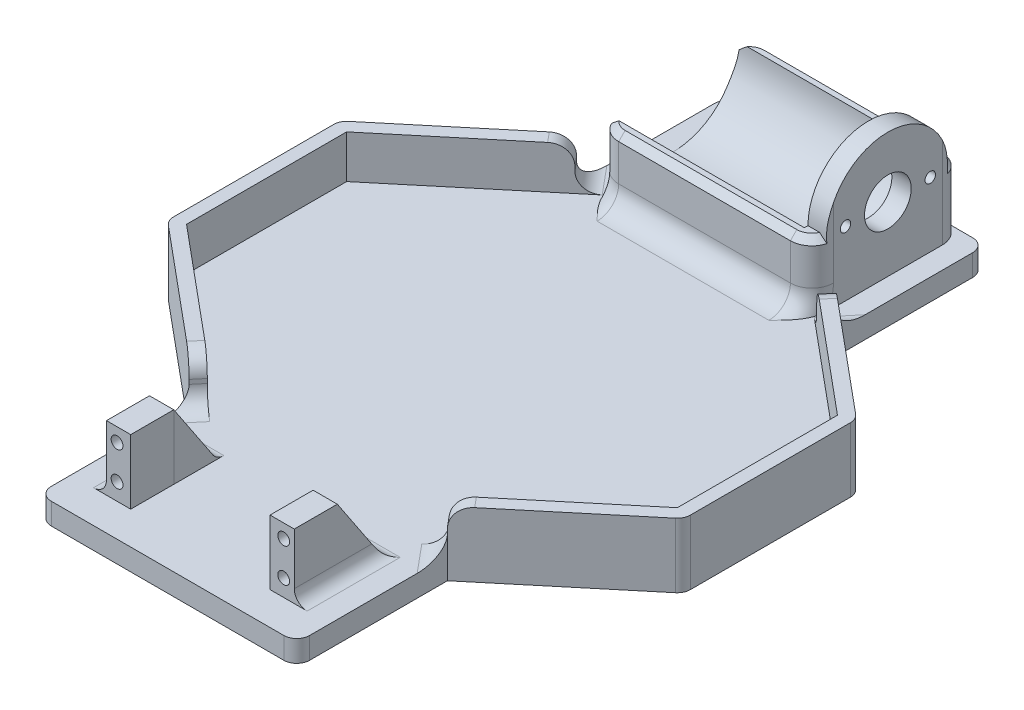
SolidWorks part; units mm, degrees
ref_plane "Front Plane" through (0, 0, 0) normal (0, 0, 1) x (1, 0, 0)
ref_plane "Top Plane" through (0, 0, 0) normal (0, 1, 0) x (1, 0, 0)
ref_plane "Right Plane" through (0, 0, 0) normal (1, 0, 0) x (0, 0, -1)
sketch "Sketch1" plane through (0, 0, 0) normal (0, 1, 0) x (1, 0, 0)
  line L0 (-34.29, 0) -> (34.29, 0)
  line L1 (0, 0) -> (0, 203.2) construction
  line L2 (-34.29, 203.2) -> (34.29, 203.2)
  line L3 (0, 101.6) -> (76.2, 101.6) construction
  line L4 (38.1, 199.39) -> (38.1, 158.75)
  line L5 (38.1, 158.75) -> (74.8291, 128.1424)
  line L6 (76.2, 125.2155) -> (76.2, 77.9845)
  line L7 (38.1, 44.45) -> (74.8291, 75.0576)
  line L8 (38.1, 3.81) -> (38.1, 44.45)
  line L9 (0, 0) -> (34.29, 0)
  line L10 (-38.1, 3.81) -> (-38.1, 44.45)
  line L11 (-38.1, 44.45) -> (-74.8291, 75.0576)
  line L12 (-76.2, 125.2155) -> (-76.2, 77.9845)
  line L13 (-38.1, 158.75) -> (-74.8291, 128.1424)
  line L14 (-38.1, 199.39) -> (-38.1, 158.75)
  arc A0 (38.1, 199.39) -> (34.29, 203.2) centre (34.29, 199.39) ccw
  arc A1 (76.2, 125.2155) -> (74.8291, 128.1424) centre (72.39, 125.2155) ccw
  arc A2 (76.2, 77.9845) -> (74.8291, 75.0576) centre (72.39, 77.9845) cw
  arc A3 (38.1, 3.81) -> (34.29, 0) centre (34.29, 3.81) cw
  arc A4 (-38.1, 3.81) -> (-34.29, 0) centre (-34.29, 3.81) ccw
  arc A5 (-76.2, 77.9845) -> (-74.8291, 75.0576) centre (-72.39, 77.9845) ccw
  arc A6 (-76.2, 125.2155) -> (-74.8291, 128.1424) centre (-72.39, 125.2155) cw
  arc A7 (-38.1, 199.39) -> (-34.29, 203.2) centre (-34.29, 199.39) cw
  point P11 (-93.4544, 210.6955)
  point P14 (38.1, 203.2)
  point P17 (76.2, 127)
  point P20 (76.2, 76.2)
  dimension "D1" = 3.81
  dimension "D2" = 203.2
  dimension "D3" = 76.2
  dimension "D4" = 38.1
  dimension "D5" = 25.4
  dimension "D6" = 44.45
extrude "Boss-Extrude1" add sketch "Sketch1" along normal blind 6.35 contours A7 L14 L13 A6 L12 A5 L11 L10 A4 L0 A3 L8 L7 A2 L6 A1 L5 L4 A0 L2 region at (0, 0, -101.6)
sketch "Sketch2" plane through (0, 6.35, 0) normal (0, 1, 0) x (1, 0, 0)
  line L0 (0, 0) -> (0, 9.6774) construction
  line L1 (-27.6987, 9.6774) -> (-27.6987, 22.3774)
  line L2 (-20.5486, 9.6774) -> (-27.6987, 9.6774)
  line L3 (20.5486, 9.6774) -> (27.6987, 9.6774)
  line L4 (-27.6987, 22.3774) -> (-20.5486, 22.3774)
  line L5 (-20.5486, 22.3774) -> (-20.5486, 9.6774)
  line L6 (27.6987, 22.3774) -> (20.5486, 22.3774)
  line L7 (27.6987, 9.6774) -> (27.6987, 22.3774)
  line L8 (20.5486, 22.3774) -> (20.5486, 9.6774)
  point P6 (0, 9.6774)
  point P12 (0, 0)
  point P14 (-29.2604, 13.1532)
  dimension "D1" = 9.6774
  dimension "D2" = 41.0972
  dimension "D4" = 12.7
extrude "Boss-Extrude2" add sketch "Sketch2" along normal blind 19.05 contours L6 L8 L3 L7 | L5 L2 L1 L4 region at (24.1236, 6.35, -16.0274)
sketch "Sketch3" plane through (-27.6987, 0, 0) normal (-1, 0, 0) x (0, 0, 1)
  line L0 (-22.3774, 25.4) -> (-35.0774, 6.35)
  line L1 (-3.81, 6.35) -> (-44.45, 6.35) construction
  line L2 (-35.0774, 6.35) -> (-22.3774, 6.35)
  line L3 (-22.3774, 6.35) -> (-22.3774, 25.4)
  dimension "D1" = 12.7
extrude "Boss-Extrude3" add sketch "Sketch3" against normal blind 7.1628
ref_plane "Plane1" through (0, 0, 0) normal (-1, 0, 0) x (0, 0, 1)
mirror "Mirror1" about plane through (0, 0, 0) normal (-1, 0, 0) of "Boss-Extrude3"
fillet "Fillet1" radius 3.81 4 edges at (27.6987, 6.35, -22.3774) (24.1173, 6.35, -35.0774) (-24.1173, 6.35, -35.0774) (-27.6987, 6.35, -22.3774)
sketch "Sketch4" plane through (0, 6.35, 0) normal (0, 1, 0) x (1, 0, 0)
  line L0 (-38.1, 158.75) -> (-74.8291, 128.1424)
  line L1 (-76.2, 125.2155) -> (-76.2, 77.9845) construction
  line L2 (-76.2, 125.2155) -> (-76.2, 77.9845)
  line L3 (-74.8291, 75.0576) -> (-38.1, 44.45)
  line L4 (-35.6609, 155.8231) -> (-72.39, 125.2155)
  line L5 (-72.39, 125.2155) -> (-72.39, 77.9845)
  line L6 (-72.39, 77.9845) -> (-35.6609, 47.3769)
  line L7 (-38.1, 44.45) -> (-35.6609, 47.3769)
  line L8 (-38.1, 158.75) -> (-35.6609, 155.8231)
  line L9 (0, 8.382) -> (0, -8.382) construction
  line L10 (35.6609, 155.8231) -> (72.39, 125.2155)
  line L11 (38.1, 158.75) -> (74.8291, 128.1424)
  line L12 (72.39, 125.2155) -> (72.39, 77.9845)
  line L13 (76.2, 125.2155) -> (76.2, 77.9845)
  line L14 (38.1, 44.45) -> (35.6609, 47.3769)
  line L15 (74.8291, 75.0576) -> (38.1, 44.45)
  line L16 (72.39, 77.9845) -> (35.6609, 47.3769)
  line L17 (38.1, 158.75) -> (35.6609, 155.8231)
  arc A0 (-74.8291, 128.1424) -> (-76.2, 125.2155) centre (-72.39, 125.2155) ccw
  arc A1 (-76.2, 77.9845) -> (-74.8291, 75.0576) centre (-72.39, 77.9845) ccw
  arc A2 (-72.39, 125.2155) -> (-72.39, 125.2155) centre (-72.39, 125.2155) ccw
  arc A3 (-72.39, 77.9845) -> (-72.39, 77.9845) centre (-72.39, 77.9845) ccw
  arc A4 (74.8291, 128.1424) -> (76.2, 125.2155) centre (72.39, 125.2155) cw
  arc A5 (76.2, 77.9845) -> (74.8291, 75.0576) centre (72.39, 77.9845) cw
  dimension "D1" = 3.81
extrude "Boss-Extrude4" add sketch "Sketch4" along normal blind 12.7
fillet "Fillet3" radius 5.715 8 edges at (36.8804, 6.35, -45.9135) (-36.8804, 6.35, -45.9135) (36.8804, 6.35, -157.2865) (-36.8804, 6.35, -157.2865) (36.8804, 19.05, -157.2865) (-36.8804, 19.05, -157.2865) (36.8804, 19.05, -45.9135) (-36.8804, 19.05, -45.9135)
sketch "Sketch6" plane through (0, 0, -9.6774) normal (0, 0, 1) x (1, 0, 0)
  line L0 (-34.29, 6.35) -> (34.29, 6.35) construction
  line L1 (-20.5359, 6.35) -> (-20.5359, 25.4) construction
  circle A0 centre (-24.5745, 11.3538) radius 1.7399
  circle A1 centre (-24.5745, 21.3614) radius 1.7399
  dimension "D4" = 3.4798
  dimension "D5" = 3.4798
  dimension "D1" = 5.0038
  dimension "D2" = 4.0386
  dimension "D3" = 15.0114
extrude "Cut-Extrude1" cut sketch "Sketch6" against normal blind 7.62
mirror "Mirror2" about plane through (0, 0, 0) normal (-1, 0, 0) of "Cut-Extrude1"
sketch "Sketch7" plane through (0, 6.35, 0) normal (0, 1, 0) x (1, 0, 0)
  line L0 (0, 203.2) -> (0, 158.3944) construction
  line L1 (-34.29, 203.2) -> (34.29, 203.2) construction
  line L3 (-31.6738, 158.3944) -> (31.6738, 158.3944)
  line L4 (-31.6738, 158.3944) -> (-31.6738, 203.2)
  line L5 (-31.6738, 203.2) -> (31.6738, 203.2)
  line L6 (31.6738, 158.3944) -> (31.6738, 203.2)
  line L7 (-31.6738, 158.3944) -> (31.6738, 203.2) construction
  line L8 (-31.6738, 203.2) -> (31.6738, 158.3944) construction
  point P5 (0, 180.7972)
  dimension "D1" = 44.8056
  dimension "D2" = 63.3476
extrude "Boss-Extrude5" add sketch "Sketch7" along normal blind 38.1
sketch "Sketch8" plane through (-31.6738, 0, 0) normal (-1, 0, 0) x (0, 0, 1)
  line L0 (-180.7972, 6.35) -> (-180.7972, 6.4897) construction
  line L1 (-161.8869, 25.4) -> (-158.3944, 25.4)
  line L2 (-203.2, 44.45) -> (-158.3944, 44.45) construction
  line L3 (-158.3944, 44.45) -> (-158.3944, 6.35) construction
  line L4 (-203.2, 44.45) -> (-158.3944, 44.45)
  line L5 (-203.2, 44.45) -> (-203.2, 25.4)
  line L6 (-203.2, 25.4) -> (-199.7075, 25.4)
  line L7 (-158.3944, 44.45) -> (-158.3944, 25.4)
  line L8 (-180.7972, 44.3103) -> (-180.7972, 44.45) construction
  arc A0 (-199.7075, 25.4) -> (-161.8869, 25.4) centre (-180.7972, 25.4) ccw
  dimension "D1" = 37.8206
extrude "Cut-Extrude2" cut sketch "Sketch8" against normal blind 57.6326
sketch "Sketch10" plane through (31.6738, 0, 0) normal (1, 0, 0) x (0, 0, -1)
  line L0 (180.7972, 6.35) -> (180.7972, 7.5184) construction
  line L4 (158.3944, 6.35) -> (203.2, 6.35) construction
  line L5 (203.2, 44.45) -> (203.2, 6.35) construction
  line L7 (158.3944, 44.45) -> (203.2, 44.45)
  line L8 (158.3944, 44.45) -> (158.3944, 25.4)
  line L9 (158.3944, 25.4) -> (162.941, 25.4)
  line L10 (203.2, 44.45) -> (203.2, 25.4)
  line L11 (198.6534, 25.4) -> (203.2, 25.4)
  arc A0 (198.6534, 25.4) -> (162.941, 25.4) centre (180.7972, 25.3746) ccw
  dimension "D2" = 35.7124
  dimension "D1" = 19.0246
extrude "Cut-Extrude3" cut sketch "Sketch10" against normal up to next
fillet "Fillet4" radius 6.35 1 edges at (0, 6.35, -158.3944)
fillet "Fillet5" radius 6.35 6 edges at (-31.6738, 8.2099, -156.5345) (31.6738, 8.2099, -156.5345) (-31.6738, 15.875, -203.2) (-31.6738, 19.05, -158.3944) (31.6738, 15.875, -203.2) (31.6738, 19.05, -158.3944)
chamfer "Chamfer1" distance 1.905 angle 45 6 edges at (29.1232, 25.4, -159.6565) (-28.6538, 25.4, -159.3376) (0, 25.4, -158.3944) (29.1232, 25.4, -201.9379) (-28.6538, 25.4, -202.2568) (0, 25.4, -203.2)
sketch "Sketch11" plane through (31.6738, 0, 0) normal (1, 0, 0) x (0, 0, -1)
  line L0 (180.7972, 43.2308) -> (180.7972, 6.35) construction
  line L1 (163.0429, 6.35) -> (196.85, 6.35) construction
  line L2 (168.3004, 25.4) -> (193.294, 25.4) construction
  arc A0 (196.85, 33.1945) -> (164.7444, 33.1945) centre (180.7972, 25.3746) ccw construction
  circle A1 centre (180.7972, 25.4) radius 6.8961
  circle A2 centre (168.3004, 25.4) radius 1.5494
  circle A3 centre (193.294, 25.4) radius 1.5494
  point P12 (180.7972, 25.4)
  dimension "D2" = 13.7922
  dimension "D4" = 3.0988
  dimension "D1" = 19.05
  dimension "D3" = 24.9936
extrude "Cut-Extrude4" cut sketch "Sketch11" against normal up to next contours A1 | A3 | A2 region at (31.6738, 25.4, -180.7972) region at (31.6738, 25.4, -193.294)
